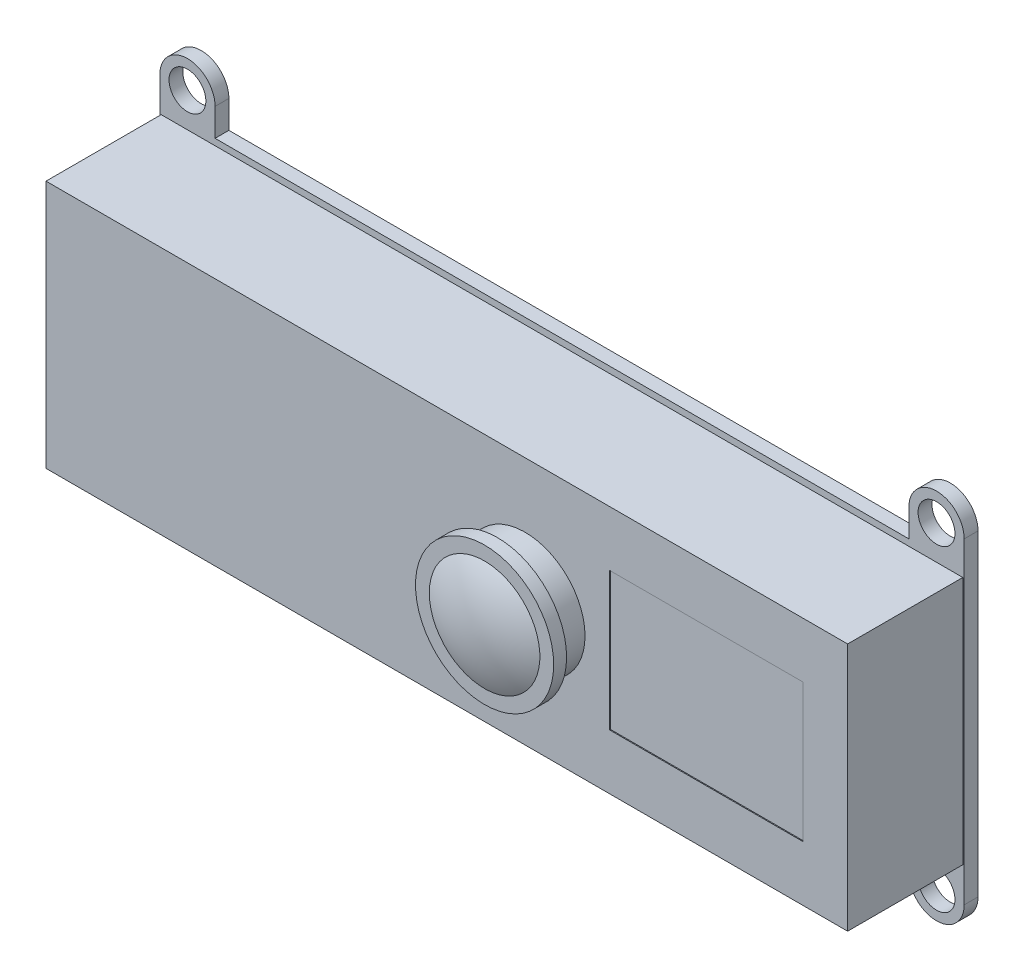
SolidWorks part; units mm, degrees
ref_plane "Alzado" through (0, 0, 0) normal (0, 0, 1) x (1, 0, 0)
ref_plane "Planta" through (0, 0, 0) normal (0, 1, 0) x (1, 0, 0)
ref_plane "Vista lateral" through (0, 0, 0) normal (1, 0, 0) x (0, 0, -1)
sketch "Croquis1" plane through (0, 0, 0) normal (0, 0, 1) x (1, 0, 0)
  line L1 (43.5, -13.5) -> (-43.5, -13.5)
  line L2 (43.5, -13.5) -> (43.5, 13.5)
  line L3 (43.5, 13.5) -> (-43.5, 13.5)
  line L4 (-43.5, -13.5) -> (-43.5, 13.5)
  line L5 (43.5, -13.5) -> (-43.5, 13.5) construction
  line L6 (43.5, 13.5) -> (-43.5, -13.5) construction
  point P0 (0, 0)
  dimension "D1" = 27
  dimension "D2" = 87
extrude "Saliente-Extruir1" add sketch "Croquis1" along normal blind 12.5
sketch "Croquis2" plane through (0, 0, 0) normal (0, 0, -1) x (-1, 0, 0)
  line L0 (-40.65, 14.2) -> (-40.65, 17.2) construction
  line L1 (43.65, -14.2) -> (-43.65, -14.2)
  line L2 (43.65, -14.2) -> (43.65, 14.2)
  line L3 (43.65, 14.2) -> (-43.65, 14.2)
  line L4 (-43.65, -14.2) -> (-43.65, 14.2)
  line L5 (43.65, -14.2) -> (-43.65, 14.2) construction
  line L6 (43.65, 14.2) -> (-43.65, -14.2) construction
  line L7 (-43.65, 14.2) -> (-43.65, 17.2)
  line L8 (-37.65, 14.2) -> (-37.65, 17.2)
  line L9 (0, 14.2) -> (0, -14.2) construction
  line L10 (-43.65, 0) -> (43.65, 0) construction
  line L11 (40.65, 14.2) -> (40.65, 17.2) construction
  line L12 (37.65, 14.2) -> (37.65, 17.2)
  line L13 (43.65, 14.2) -> (43.65, 17.2)
  line L14 (40.65, -14.2) -> (40.65, -17.2) construction
  line L15 (43.65, -14.2) -> (43.65, -17.2)
  line L16 (37.65, -14.2) -> (37.65, -17.2)
  line L17 (-40.65, -14.2) -> (-40.65, -17.2) construction
  line L18 (-37.65, -14.2) -> (-37.65, -17.2)
  line L19 (-43.65, -14.2) -> (-43.65, -17.2)
  arc A1 (-37.65, 17.2) -> (-43.65, 17.2) centre (-40.65, 17.2) ccw
  circle A2 centre (-40.65, 17.2) radius 2
  circle A3 centre (40.65, 17.2) radius 2
  arc A4 (37.65, 17.2) -> (43.65, 17.2) centre (40.65, 17.2) cw
  arc A5 (37.65, -17.2) -> (43.65, -17.2) centre (40.65, -17.2) ccw
  circle A6 centre (40.65, -17.2) radius 2
  circle A7 centre (-40.65, -17.2) radius 2
  arc A8 (-37.65, -17.2) -> (-43.65, -17.2) centre (-40.65, -17.2) cw
  point P0 (0, 0)
  point P8 (-40.65, 14.2)
  point P23 (40.65, 14.2)
  point P30 (40.65, -14.2)
  point P37 (-40.65, -14.2)
  line M5 (43.5, -13.5) -> (43.5, 13.5)
  line M6 (43.5, 13.5) -> (-43.5, 13.5)
  line M7 (-43.5, 13.5) -> (-43.5, -13.5)
  line M8 (-43.5, -13.5) -> (43.5, -13.5)
  dimension "D4" = 3
  dimension "D3" = 3
  dimension "D5" = 1
  dimension "D1" = 28.4
  dimension "D2" = 87.3
extrude "Saliente-Extruir3" add sketch "Croquis2" along normal blind 1.5 contours A4 L12 L3 L13 A3 | L16 A5 L15 L1 A6 | A8 L18 L1 L19 A7 | L8 A1 L7 L3 A2 | L4 L1 L2 L3 M5 M8 M7 M6 | M8 M5 M6 M7 region at (-43.5651, -15.7, 0) region at (-40.65, -14.1082, 0) region at (-40.65, 14.2849, 0) region at (37.7349, -15.7, 0) region at (40.65, 14.2849, 0) region at (0, 0, 0)
sketch "Croquis3" plane through (0, 0, 12.5) normal (0, 0, 1) x (1, 0, 0)
  line L0 (-43.5, 0) -> (43.65, 0) construction
  line L1 (-43.5, 13.5) -> (-43.5, -13.5) construction
  line L2 (43.65, -17.2) -> (43.65, 17.2) construction
  circle A0 centre (8.5, 0) radius 6.5
  dimension "D1" = 13
  dimension "D2" = 52
extrude "Saliente-Extruir4" add sketch "Croquis3" along normal blind 3
sketch "Croquis4" plane through (0, 0, 15.5) normal (0, 0, 1) x (1, 0, 0)
  circle A0 centre (8.5, 0) radius 7.5
  dimension "D1" = 15
extrude "Saliente-Extruir5" add sketch "Croquis4" along normal blind 1.4
ref_plane "Plano1" through (0, 0, 8.9) normal (0, 0, 1) x (1, 0, 0)
ref_plane "Plano2" through (0, 0, 0) normal (0, 1, 0) x (1, 0, 0)
sketch "Croquis7" plane through (0, 0, 0) normal (0, 1, 0) x (1, 0, 0)
  line L0 (8.5, -16.9) -> (8.5, 1.5) construction
  line L1 (1, -16.9) -> (16, -16.9) construction
  line L2 (-37.65, 1.5) -> (37.65, 1.5) construction
  line L3 (1, -15.5) -> (1, -16.9) construction
  line L4 (8.5, -18.4) -> (-5.1937, -18.4) construction
  line L5 (2.5, -16.9) -> (14.5, -16.9)
  line L6 (14.5, -16.9) -> (2.5, -16.9)
  line L7 (8.5, -16.9) -> (8.5, -18.4)
  arc A1 (2.5, -16.9) -> (14.5, -16.9) centre (8.5, -5.65) ccw
  dimension "D1" = 1.5
  dimension "D2" = 1.5
revolve "Revolución3" add sketch "Croquis7" angle 360 about L7 region at (10.7688, 0, 17.5031)
sketch "Croquis8" plane through (0, 0, 12.5) normal (0, 0, 1) x (1, 0, 0)
  line L0 (6.875, 0) -> (-6.875, 0) construction
  line L1 (38.65, -7.5) -> (17.65, -7.5)
  line L2 (38.65, -7.5) -> (38.65, 7.5)
  line L3 (38.65, 7.5) -> (17.65, 7.5)
  line L4 (17.65, -7.5) -> (17.65, 7.5)
  line L5 (38.65, -7.5) -> (17.65, 7.5) construction
  line L6 (38.65, 7.5) -> (17.65, -7.5) construction
  line L7 (43.65, -17.2) -> (43.65, 17.2) construction
  point P0 (28.15, 0)
  dimension "D1" = 5
  dimension "D2" = 21
  dimension "D3" = 15
extrude "Cortar-Extruir2" cut sketch "Croquis8" against normal blind 0.1
sketch "Croquis9" plane through (-43.5, 0, 0) normal (-1, 0, 0) x (0, 0, 1)
  line L0 (1.75, -3.25) -> (1.75, 3.25) construction
  line L1 (6.875, 0) -> (-6.875, 0) construction
  line L2 (0, -3.25) -> (0, 3.25)
  line L3 (3.5, -3.25) -> (3.5, 3.25)
  line L4 (0, -17.2) -> (0, 17.2) construction
  line L5 (0.3, -3.25) -> (0.3, 3.25)
  line L6 (3.2, -3.25) -> (3.2, 3.25)
  line L7 (1.5, -3.25) -> (1.5, 3.25)
  line L8 (2, -3.25) -> (2, 3.25)
  arc A0 (0, -3.25) -> (3.5, -3.25) centre (1.75, -3.25) ccw
  arc A1 (3.5, 3.25) -> (0, 3.25) centre (1.75, 3.25) ccw
  arc A2 (3.2, 3.25) -> (0.3, 3.25) centre (1.75, 3.25) ccw
  arc A3 (0.3, -3.25) -> (3.2, -3.25) centre (1.75, -3.25) ccw
  arc A4 (2, 3.25) -> (1.5, 3.25) centre (1.75, 3.25) ccw
  arc A5 (1.5, -3.25) -> (2, -3.25) centre (1.75, -3.25) ccw
  point P4 (1.75, 0)
  line M9 (0, 13.5) -> (0, -13.5)
  dimension "D2" = 6.5
  dimension "D1" = 3.5
  dimension "D3" = 0.3
  dimension "D4" = 1.5
extrude "Saliente-Extruir6" add sketch "Croquis9" along normal blind 1.7 contours L7 A5 L8 A4 | L3 A1 A0 A3 L5 A2 L6 M9 region at (-43.5, 0, 0.1059) region at (-43.5, 0, 1.75)
